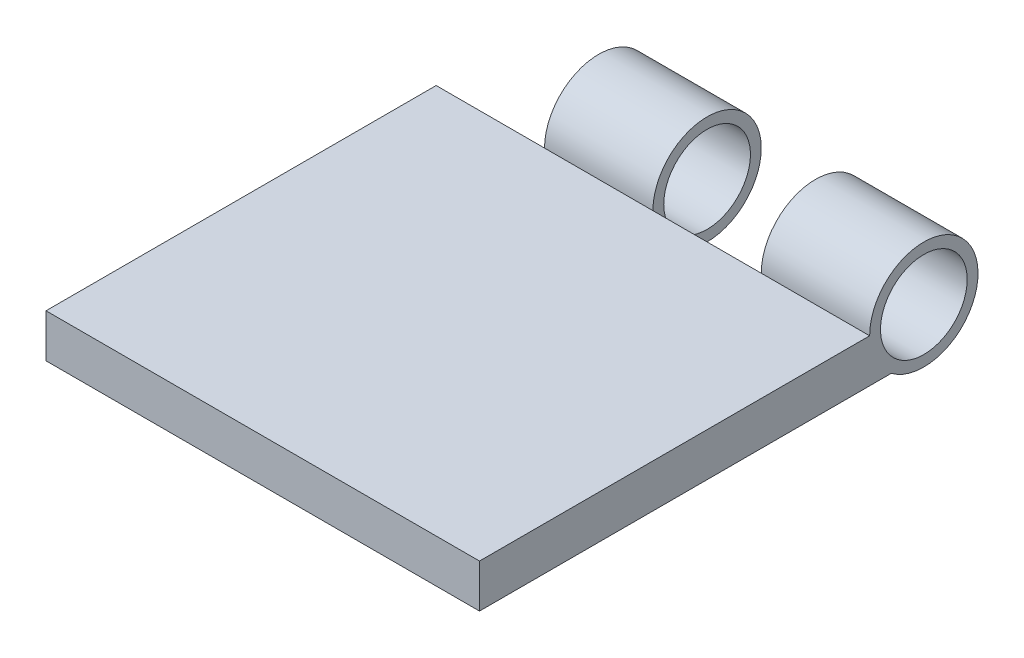
SolidWorks part; units mm, degrees
ref_plane "Front Plane" through (0, 0, 0) normal (0, 0, 1) x (1, 0, 0)
ref_plane "Top Plane" through (0, 0, 0) normal (0, 1, 0) x (1, 0, 0)
ref_plane "Right Plane" through (0, 0, 0) normal (1, 0, 0) x (0, 0, -1)
sketch "Sketch2" plane through (0, 0, 0) normal (0, 1, 0) x (1, 0, 0)
  line L1 (-10, -9) -> (10, -9)
  line L2 (-10, -9) -> (-10, 9)
  line L3 (-10, 9) -> (10, 9)
  line L4 (10, -9) -> (10, 9)
  line L5 (-10, -9) -> (10, 9) construction
  line L6 (-10, 9) -> (10, -9) construction
  point P0 (0, 0)
  dimension "D1" = 18
  dimension "D2" = 20
extrude "Boss-Extrude2" add sketch "Sketch2" along normal blind 2
sketch "Sketch3" plane through (10, 0, 0) normal (1, 0, 0) x (0, 0, -1)
  line L0 (9, 2) -> (14, 2)
  line L1 (9, 0) -> (10, 0)
  arc A0 (10, 0) -> (9, 2) centre (11.5, 2) ccw
  line M2 (9, 0) -> (9, 2)
  dimension "D1" = 5
extrude "Boss-Extrude3" add sketch "Sketch3" against normal blind 5 contours L1 A0 L0 M2 | L0 A0 region at (10, 3.061, -11.5) region at (10, 0.9123, -11.372)
ref_plane "Plane1" through (2.5, 0, 0) normal (-1, 0, 0) x (0, 0, 1)
mirror "Mirror1" about plane through (2.5, 0, 0) normal (-1, 0, 0) of "Boss-Extrude3"
sketch "Sketch4" plane through (10, 0, 0) normal (1, 0, 0) x (0, 0, -1)
  circle A0 centre (11.5, 2) radius 2
  dimension "D1" = 4
extrude "Cut-Extrude1" cut sketch "Sketch4" against normal through all
